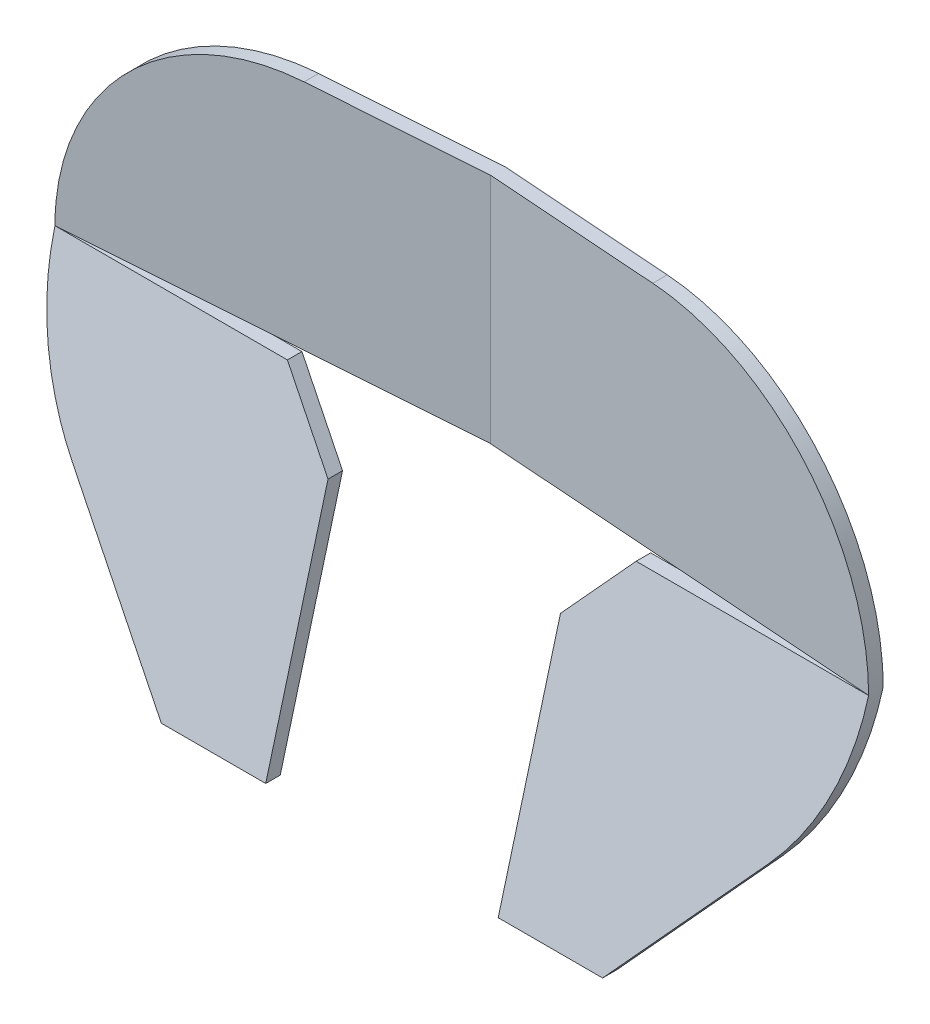
SolidWorks part; units mm, degrees
ref_plane "Front Plane" through (0, 0, 0) normal (0, 0, 1) x (1, 0, 0)
ref_plane "Top Plane" through (0, 0, 0) normal (0, 1, 0) x (1, 0, 0)
ref_plane "Right Plane" through (0, 0, 0) normal (1, 0, 0) x (0, 0, -1)
sketch "Sketch1" plane through (0, 0, 0) normal (0, 0, 1) x (1, 0, 0)
  line L0 (341.7406, 162.4689) -> (290.9406, 105.3189)
  line L3 (36.9406, 365.6689) -> (341.7406, 365.6689)
  line L8 (36.9406, 162.4689) -> (87.7406, 105.3189)
  line L11 (87.7406, 162.4689) -> (290.9406, 162.4689)
  line L12 (493.6142, 27.4702) -> (382.1908, -97.8811)
  line L13 (290.9406, -97.8811) -> (290.9406, 105.3189)
  line L16 (382.1908, -97.8811) -> (290.9406, -97.8811)
  line L17 (87.7406, 105.3189) -> (87.7406, -97.8811)
  line L18 (87.7406, -97.8811) -> (-3.5096, -97.8811)
  line L19 (-3.5096, -97.8811) -> (-114.933, 27.4702)
  line L20 (36.9406, 162.4689) -> (87.7406, 162.4689)
  line L21 (341.7406, 162.4689) -> (290.9406, 162.4689)
  arc A2 (36.9406, 365.6689) -> (-114.933, 27.4702) centre (36.9406, 162.4689) ccw
  arc A3 (341.7406, 365.6689) -> (493.6142, 27.4702) centre (341.7406, 162.4689) cw
  dimension "D1" = 203.2
  dimension "D4" = 203.2
  dimension "D5" = 203.2
  dimension "D2" = 203.2
  dimension "D3" = 57.15
  dimension "D6" = 304.8
  dimension "D7" = 203.2
  dimension "D8" = 50.8
  dimension "D9" = 50.8
  dimension "D10" = 203.2
extrude "Boss-Extrude1" add sketch "Sketch1" along normal blind 152.4 contours L3 A3 L12 L16 L13 L0 L21 L11 L20 L8 L17 L18 L19 A2
sketch "Sketch4" plane through (0, 365.6689, 0) normal (0, 1, 0) x (1, 0, 0)
  line L0 (189.3406, 0) -> (-166.2594, -25.4)
  line L1 (36.9406, 0) -> (341.7406, 0) construction
  line L2 (-166.2594, 0) -> (-166.2594, -152.4) construction
  line L3 (-166.2594, -25.4) -> (-166.2594, 0)
  line L4 (36.9406, 0) -> (-166.2594, 0) construction
  line L5 (-166.2594, 0) -> (189.3406, 0)
  line L6 (189.3406, 0) -> (544.9406, 0)
  line L7 (544.9406, 0) -> (544.9406, -25.4)
  line L8 (544.9406, -25.4) -> (189.3406, 0)
  line L9 (-166.5087, -38.1) -> (189.0913, -12.7)
  line L10 (189.0913, -12.7) -> (544.9406, -38.1)
  line L11 (544.9406, -152.4) -> (544.9406, 0) construction
  line L12 (544.9406, -38.1) -> (544.9406, -152.4)
  line L13 (341.7406, -152.4) -> (544.9406, -152.4) construction
  line L14 (544.9406, -152.4) -> (-166.5087, -152.4)
  line L15 (-166.2594, -152.4) -> (36.9406, -152.4) construction
  line L16 (-166.5087, -152.4) -> (-166.5087, -38.1)
  line M9 (36.9406, 0) -> (36.9406, -152.4)
  line M10 (36.9406, -152.4) -> (341.7406, -152.4)
  line M11 (341.7406, -152.4) -> (341.7406, 0)
  dimension "D1" = 12.7
  dimension "D2" = 12.7
  dimension "D3" = 12.7
  dimension "D4" = 25.4
  dimension "D5" = 25.4
extrude "Cut-Extrude4" cut sketch "Sketch4" against normal blind 203.2 contours L8 L7 L6 M11 | L10 L9 M9 M10 M11 | L16 L14 L9 M9 | L14 L12 L10 M11 | L0 L3 L5 | L6 L7 L8 region at (456.8873, 365.6689, 9.5552) region at (-62.7573, 365.6689, 91.5446) region at (189.3319, 365.6689, 85.2337) region at (441.32, 365.6689, 91.5519)
sketch "Sketch5" plane through (87.7406, 0, 0) normal (1, 0, 0) x (0, 0, -1)
  line L0 (-38.1, 162.4689) -> (-107.8606, -97.8811)
  line L1 (-152.4, -97.8811) -> (0, -97.8811) construction
  line L2 (-107.8606, -97.8811) -> (-152.4, -97.8811)
  line L3 (-152.4, -97.8811) -> (-152.4, 162.4689)
  line L4 (-152.4, 162.4689) -> (-38.1, 162.4689)
  line L5 (-25.4, 162.4689) -> (-95.1606, -97.8811)
  line L6 (-95.1606, -97.8811) -> (0, -97.8811)
  line L7 (0, -97.8811) -> (0, 162.4689)
  line L8 (0, 162.4689) -> (-25.4, 162.4689)
  line M3 (0, -97.8811) -> (0, 105.3189)
  line M4 (0, 105.3189) -> (-152.4, 105.3189)
  line M6 (-152.4, -97.8811) -> (0, -97.8811)
  dimension "D1" = 75
extrude "Cut-Extrude5" cut sketch "Sketch5" against normal through all both and the other way through all contours L5 M4 M6 M3 | L7 L8 L5 M4 | L4 L0 L2 L3 region at (87.7406, -9.8521, 35.7866) region at (87.7406, 131.6877, 16.8239)
